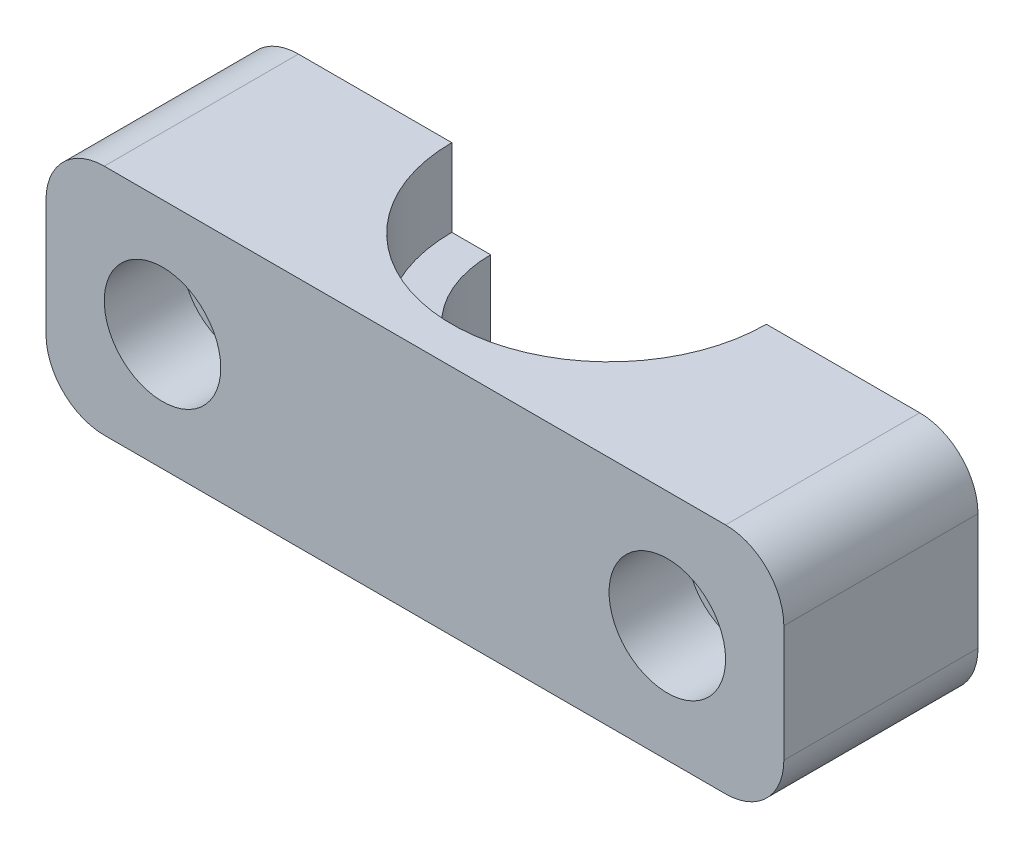
SolidWorks part; units mm, degrees
ref_plane "Front" through (0, 0, 0) normal (0, 0, 1) x (1, 0, 0)
ref_plane "Top" through (0, 0, 0) normal (0, 1, 0) x (1, 0, 0)
ref_plane "Right" through (0, 0, 0) normal (1, 0, 0) x (0, 0, -1)
sketch "Esboço1" plane through (0, 0, 0) normal (0, 0, 1) x (1, 0, 0)
  line L0 (-13, 0) -> (13, 0) construction
  line L1 (-19, -6) -> (19, -6)
  line L2 (-19, -6) -> (-19, 6)
  line L3 (-19, 6) -> (19, 6)
  line L4 (19, -6) -> (19, 6)
  line L5 (-19, -6) -> (19, 6) construction
  line L6 (-19, 6) -> (19, -6) construction
  circle A0 centre (-13, 0) radius 1.7
  circle A1 centre (13, 0) radius 1.7
  point P0 (0, 0)
  point P10 (0, 0)
  dimension "D4" = 3.4
  dimension "D1" = 38
  dimension "D2" = 12
  dimension "D3" = 26
extrude "Ressalto-extrusão1" add sketch "Esboço1" along normal blind 10 contours L1 L4 L3 L2 A1 A0 region at (0, 0, 0)
fillet "Filete1" radius 3 4 edges at (-19, -6, 5) (-19, 6, 5) (19, -6, 5) (19, 6, 5)
sketch "Esboço2" plane through (0, 6, 0) normal (0, 1, 0) x (1, 0, 0)
  line L0 (-16, 0) -> (16, 0) construction
  circle A0 centre (0, 0) radius 8.1
  dimension "D1" = 16.2
extrude "Corte-extrusão1" cut sketch "Esboço2" against normal blind 4
sketch "Esboço3" plane through (0, 2, 0) normal (0, 1, 0) x (1, 0, 0)
  line L0 (8.1, 0) -> (-8.1, 0) construction
  circle A0 centre (0, 0) radius 6.1
  dimension "D1" = 12.2
extrude "Corte-extrusão2" cut sketch "Esboço3" against normal blind 5
extrude "Corte-extrusão3" cut sketch "Esboço2<2>" against normal blind 4 from surface starting at face at (0, -3, 3.05)
sketch "Esboço2<2>" plane through (0, 6, 0) normal (0, 1, 0) x (1, 0, 0) same geometry as "Esboço2"
sketch "Esboço4" plane through (0, 0, 10) normal (0, 0, 1) x (1, 0, 0)
  circle A0 centre (-13, 0) radius 3
  circle A1 centre (13, 0) radius 3
  dimension "D1" = 6
extrude "Corte-extrusão4" cut sketch "Esboço4" against normal blind 4
